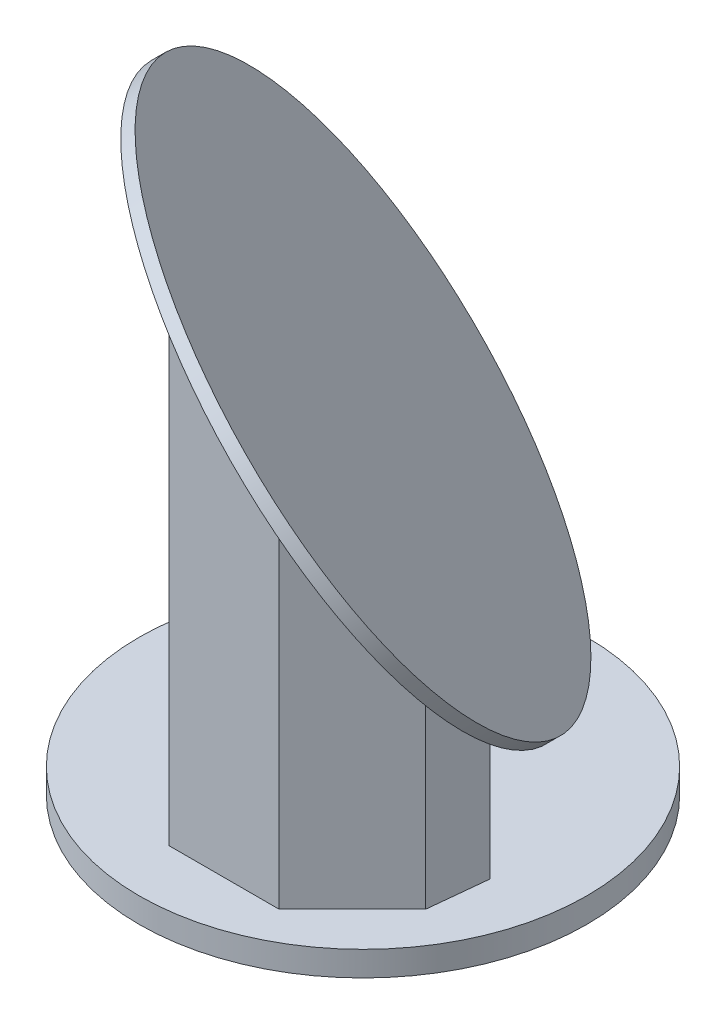
SolidWorks part; units mm, degrees
ref_plane "前视基准面" through (0, 0, 0) normal (0, 0, 1) x (1, 0, 0)
ref_plane "上视基准面" through (0, 0, 0) normal (0, 1, 0) x (1, 0, 0)
ref_plane "右视基准面" through (0, 0, 0) normal (1, 0, 0) x (0, 0, -1)
sketch "草图1" plane through (0, 0, 0) normal (0, 1, 0) x (1, 0, 0)
  line L1 (0, 0) -> (1, 0) construction
  line L2 (0, 0) -> (0, 1) construction
  line L3 (0, 1) -> (1, 1) construction
  line L4 (1, 0) -> (1, 1) construction
  dimension "D1" = 1
  dimension "D2" = 1
ref_plane "基准面1" through (0, 1, 0) normal (0, 1, 0) x (1, 0, 0)
sketch "草图2" plane through (0, 1, 0) normal (0, 1, 0) x (1, 0, 0)
  line L1 (0, 0) -> (1, 0) construction
  line L2 (0, 0) -> (0, 1) construction
  line L3 (0, 1) -> (1, 1) construction
  line L4 (1, 0) -> (1, 1) construction
ref_axis "基准轴1" through (0, 0, 0) along (0.5774, 0.5774, -0.5774)
ref_plane "基准面2" through (0, 0, 0) normal (0.5774, 0.5774, -0.5774) x (-0.4082, -0.4082, -0.8165)
sketch "草图3" plane through (0, 0, 0) normal (0.5774, 0.5774, -0.5774) x (-0.4082, -0.4082, -0.8165)
  circle A0 centre (0, 0) radius 112.5
  dimension "D1" = 225
ref_plane "基准面3" through (0, -140, 0) normal (0, 1, 0) x (1, 0, 0)
extrude "凸台-拉伸5" add sketch "草图3" against normal blind 5 contours A0
sketch "草图5" plane through (0, -140, 0) normal (0, 1, 0) x (1, 0, 0)
  line L0 (0, 0) -> (45.9279, 45.9279) construction
  line L1 (0, 0) -> (1, 1) construction
  line L15 (-37.1581, 62.4465) -> (-66.7186, 32.886)
  line L16 (-66.7186, 32.886) -> (-66.7186, -11.4512)
  line L25 (-66.7186, -11.4512) -> (-11.4512, -66.7186)
  line L26 (64.8498, -13.7522) -> (-13.7522, 64.8498)
  line L27 (-13.7522, 64.8498) -> (-37.1581, 62.4465)
  line L28 (64.8498, -13.7522) -> (62.4465, -37.1581)
  line L29 (62.4465, -37.1581) -> (32.886, -66.7186)
  line L30 (32.886, -66.7186) -> (-11.4512, -66.7186)
  ellipse E0 centre (0, 0) end of major axis (79.5495, -79.5495) minor radius 64.9519 construction
  point P10 (-8.7992, 68.0048)
  point P15 (0, 0)
  point P18 (25.5488, 25.5488)
  point P21 (-39.0849, -39.0849)
extrude "凸台-拉伸1" add sketch "草图5" along normal up to surface (80.2422 mm away) up to face at (-82.4363, 76.6628, 2.8868)
sketch "草图8" plane through (0, -140, 0) normal (0, 1, 0) x (1, 0, 0)
  circle A0 centre (0, 0) radius 90.2477
extrude "凸台-拉伸2" add sketch "草图8" along normal blind 10
equation "\"drive_od\"= 225mm"
equation "\"D1@草图3\"=\"drive_od\""
